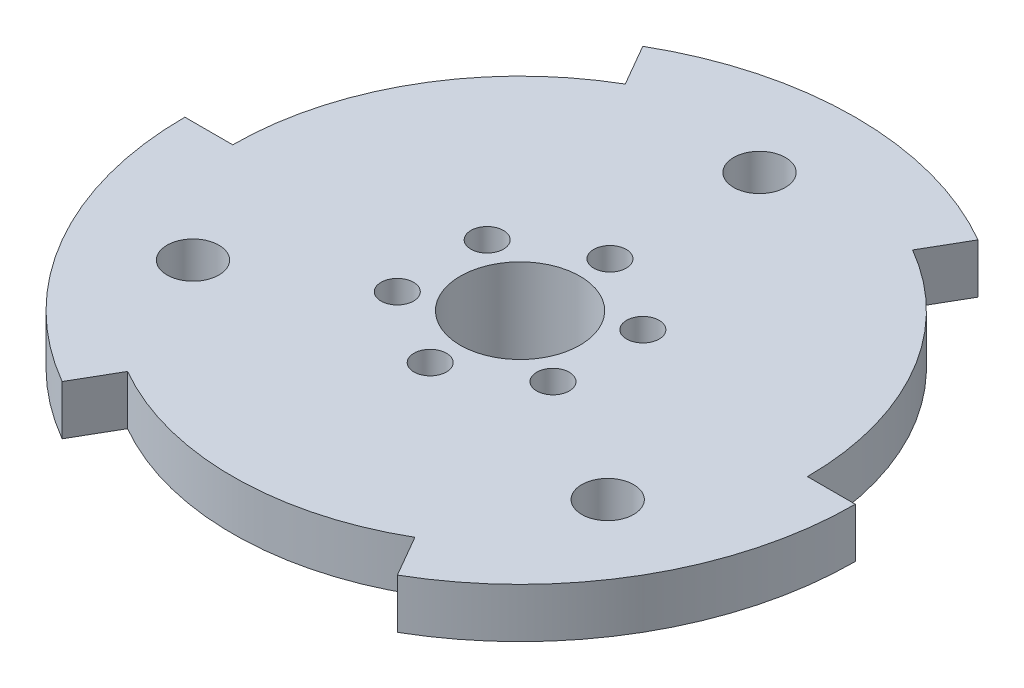
SolidWorks part; units mm, degrees
ref_plane "Front Plane" through (0, 0, 0) normal (0, 0, 1) x (1, 0, 0)
ref_plane "Top Plane" through (0, 0, 0) normal (0, 1, 0) x (1, 0, 0)
ref_plane "Right Plane" through (0, 0, 0) normal (1, 0, 0) x (0, 0, -1)
sketch "Sketch7" plane through (0, 0, 0) normal (0, 1, 0) x (1, 0, 0)
  line L1 (-11.3137, -11.3137) -> (11.3137, -11.3137)
  line L2 (-11.3137, -11.3137) -> (-11.3137, 11.3137)
  line L3 (-11.3137, 11.3137) -> (11.3137, 11.3137)
  line L4 (11.3137, -11.3137) -> (11.3137, 11.3137)
  line L5 (-11.3137, -11.3137) -> (11.3137, 11.3137) construction
  line L6 (-11.3137, 11.3137) -> (11.3137, -11.3137) construction
  circle A0 centre (0, 0) radius 16.1
  point P0 (0, 0)
  dimension "D1" = 32
extrude "Boss-Extrude2" add sketch "Sketch7" along normal blind 8.2 contours L1 L4 L3 L2 | A0 L4 L1 L2 L3 region at (0, 0, 0) region at (-15.6446, 0, 0)
sketch "Sketch1" plane through (0, 8.2, 0) normal (0, 1, 0) x (1, 0, 0)
  line L0 (0, 0) -> (0, 35.4208) construction
  line L1 (-20, -20) -> (20, -20)
  line L2 (-20, -20) -> (-20, 20)
  line L3 (-20, 20) -> (20, 20)
  line L4 (20, -20) -> (20, 20)
  line L5 (-20, -20) -> (20, 20) construction
  line L6 (-20, 20) -> (20, -20) construction
  line L7 (17.5, 30.3109) -> (15, 25.9808)
  line L8 (-17.5, 30.3109) -> (-15, 25.9808)
  line L9 (17.5, -30.3109) -> (15, -25.9808)
  line L10 (35, 0) -> (30, 0)
  line L11 (-35, 0) -> (-30, 0)
  line L12 (-17.5, -30.3109) -> (-15, -25.9808)
  circle A0 centre (0, 0) radius 6.25
  circle A1 centre (0, 25) radius 2.7073
  circle A2 centre (21.6506, -12.5) radius 2.7073
  circle A3 centre (-21.6506, -12.5) radius 2.7073
  circle A4 centre (0, 0) radius 30
  arc A5 (17.5, 30.3109) -> (-17.5, 30.3109) centre (0, 0) ccw
  arc A6 (17.5, -30.3109) -> (35, 0) centre (0, 0) ccw
  arc A7 (-35, 0) -> (-17.5, -30.3109) centre (0, 0) ccw
  point P0 (0, 0)
  point P18 (0, 0)
  point P21 (0, 35)
  point P34 (0, 0)
  dimension "D2" = 12.5
  dimension "D6" = 60
  dimension "D7" = 5
  dimension "D8" = 35
  dimension "D9" = 3
  dimension "D1" = 25
  dimension "D3" = 40
  dimension "D4" = 40
  dimension "D5" = 3
extrude "Boss-Extrude1" add sketch "Sketch1" along normal blind 5.18 contours L11 A7 L12 A4 | L9 A6 L10 A4 | L7 A5 L8 A4 | L2 A3 | L4 A2 | A1 | L2 A3 | L4 A2 | A0 | A4 region at (-21.9823, 8.2, 12.5) region at (-19.5694, 8.2, 12.5) region at (19.5694, 8.2, 12.5) region at (21.9823, 8.2, 12.5) region at (0, 8.2, -31.0964) region at (26.9303, 8.2, 15.5482) region at (-26.9303, 8.2, 15.5482) region at (0, 8.2, 0) region at (0, 8.2, -25)
sketch "Sketch5" [suppressed] plane through (0, 0, 0) normal (1, 0, 0) x (0, 0, -1)
  line L0 (-10.331, 15) -> (10.331, 0) construction
  line L1 (10, 5) -> (-10, 5)
  line L2 (10, 5) -> (10, 10)
  line L3 (10, 10) -> (-10, 10)
  line L4 (-10, 5) -> (-10, 10)
  line L5 (10, 5) -> (-10, 10) construction
  line L6 (10, 10) -> (-10, 5) construction
  line L7 (20, 7.5) -> (-20, 7.5) construction
  line L8 (20, 15) -> (20, 0) construction
  line L9 (-20, 15) -> (-20, 0) construction
  line L10 (-10.3541, 15) -> (-10.3078, 15) construction
  line L11 (-10.3541, 0) -> (20, 0) construction
  point P0 (0, 7.5)
  dimension "D1" = 20
  dimension "D2" = 5
sketch "Sketch3" [suppressed] plane through (0, 0, -20) normal (0, 0, -1) x (-1, 0, 0)
  line L3 (15.1539, 15) -> (15.1539, 3) construction
  line L4 (20, 15) -> (10.3078, 15) construction
  circle A0 centre (15.1539, 3) radius 1.6
  dimension "D2" = 3.2
  dimension "D1" = 12
sketch "Sketch2" [suppressed] plane through (0, 0, 20) normal (0, 0, 1) x (1, 0, 0)
  line L0 (0, 27.8717) -> (0, -11.9207) construction
  line L1 (20, 2) -> (10, 2)
  line L3 (10, 2) -> (10, 0)
  line L4 (-20, 0) -> (20, 0) construction
  line L5 (20, 15) -> (20, 0) construction
  circle A0 centre (10, 2) radius 1.6
  circle A1 centre (-10, 2) radius 1.6
  dimension "D3" = 3.2
  dimension "D1" = 10
  dimension "D2" = 2
sketch "Sketch6" plane through (0, 13.38, 0) normal (0, 1, 0) x (1, 0, 0)
  circle A9 centre (0, -9.385) radius 1.7
  circle A10 centre (-8.1276, -4.6925) radius 1.7
  circle A11 centre (-8.1276, 4.6925) radius 1.7
  circle A12 centre (0, 9.385) radius 1.7
  circle A13 centre (8.1276, 4.6925) radius 1.7
  circle A14 centre (8.1276, -4.6925) radius 1.7
  point P16 (0, 0)
  dimension "D2" = 9.385
  dimension "D1" = 3.4
  dimension "D3" = 9.385
extrude "Cut-Extrude1" cut sketch "Sketch6" along normal through all and the other way through all
fillet "Fillet2" [suppressed] radius 5
sketch "Sketch9" plane through (0, 13.38, 0) normal (0, 1, 0) x (1, 0, 0)
  line L6 (-30, 0) -> (-35, 0)
  line L7 (-17.5, -30.3109) -> (-15, -25.9808)
  line L8 (15, -25.9808) -> (17.5, -30.3109)
  line L9 (35, 0) -> (30, 0)
  line L10 (15, 25.9808) -> (17.5, 30.3109)
  line L11 (-17.5, 30.3109) -> (-15, 25.9808)
  line L12 (-30, 0) -> (-35, 0)
  line L13 (-17.5, -30.3109) -> (-15, -25.9808)
  line L14 (15, -25.9808) -> (17.5, -30.3109)
  line L15 (35, 0) -> (30, 0)
  line L16 (15, 25.9808) -> (17.5, 30.3109)
  line L17 (-17.5, 30.3109) -> (-15, 25.9808)
  arc A6 (-35, 0) -> (-17.5, -30.3109) centre (0, 0) ccw
  arc A7 (-15, -25.9808) -> (15, -25.9808) centre (0, 0) ccw
  arc A8 (17.5, -30.3109) -> (35, 0) centre (0, 0) ccw
  arc A9 (30, 0) -> (15, 25.9808) centre (0, 0) ccw
  arc A10 (17.5, 30.3109) -> (-17.5, 30.3109) centre (0, 0) ccw
  arc A11 (-15, 25.9808) -> (-30, 0) centre (0, 0) ccw
  arc A12 (-35, 0) -> (-17.5, -30.3109) centre (0, 0) ccw
  arc A13 (-15, -25.9808) -> (15, -25.9808) centre (0, 0) ccw
  arc A14 (17.5, -30.3109) -> (35, 0) centre (0, 0) ccw
  arc A15 (30, 0) -> (15, 25.9808) centre (0, 0) ccw
  arc A16 (17.5, 30.3109) -> (-17.5, 30.3109) centre (0, 0) ccw
  arc A17 (-15, 25.9808) -> (-30, 0) centre (0, 0) ccw
  circle M14 centre (8.1276, -4.6925) radius 1.7
  circle M15 centre (8.1276, 4.6925) radius 1.7
  circle M16 centre (0, 9.385) radius 1.7
  circle M17 centre (-8.1276, 4.6925) radius 1.7
  circle M18 centre (-8.1276, -4.6925) radius 1.7
  circle M31 centre (21.6506, -12.5) radius 2.7073
  circle M32 centre (0, 25) radius 2.7073
  circle M33 centre (-21.6506, -12.5) radius 2.7073
  circle M34 centre (0, 0) radius 6.25
  dimension "D1" = 0
extrude "Cut-Extrude2" cut sketch "Sketch9" against normal through all contours M33 | M34 | M31 | M32 | M14 | M15 | M16 | M17 | M18 region at (8.1276, 13.38, 4.6925) region at (8.1276, 13.38, -4.6925) region at (0, 13.38, -9.385) region at (-8.1276, 13.38, -4.6925) region at (-8.1276, 13.38, 4.6925) region at (21.6506, 13.38, 12.5) region at (0, 13.38, -25) region at (-21.6506, 13.38, 12.5) region at (0, 13.38, 0)
